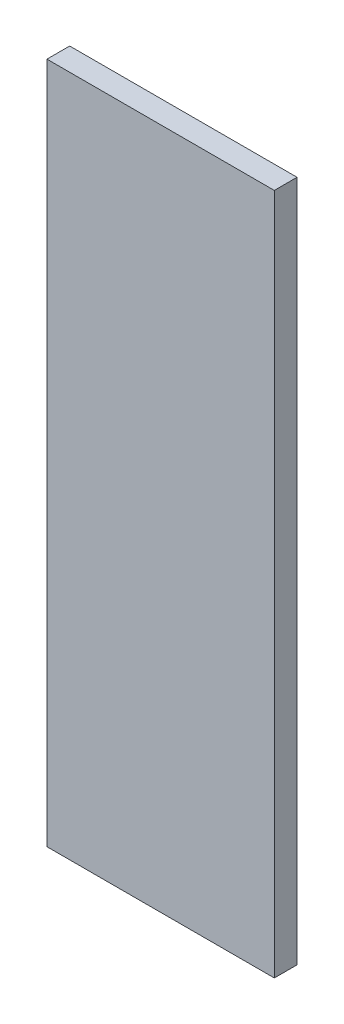
SolidWorks part; units mm, degrees
ref_plane "Front Plane" through (0, 0, 0) normal (0, 0, 1) x (1, 0, 0)
ref_plane "Top Plane" through (0, 0, 0) normal (0, 1, 0) x (1, 0, 0)
ref_plane "Right Plane" through (0, 0, 0) normal (1, 0, 0) x (0, 0, -1)
sketch "Sketch1" plane through (0, 0, 0) normal (0, 0, 1) x (1, 0, 0)
  line L1 (50, -150) -> (-50, -150)
  line L2 (50, -150) -> (50, 150)
  line L3 (50, 150) -> (-50, 150)
  line L4 (-50, -150) -> (-50, 150)
  line L5 (50, -150) -> (-50, 150) construction
  line L6 (50, 150) -> (-50, -150) construction
  point P0 (0, 0)
  dimension "D1" = 100
  dimension "D2" = 300
extrude "Boss-Extrude1" add sketch "Sketch1" along normal blind 10
sketch "Sketch2" plane through (0, 0, 10) normal (0, 0, 1) x (1, 0, 0)
  line L0 (-50, 150) -> (-50, -150) construction
  line L1 (50, 150) -> (-50, 150) construction
  line L2 (-50, -150) -> (50, -150) construction
  line L4 (0, -5.5) -> (0, 5.5) construction
  circle A0 centre (-45, 122) radius 1.5
  circle A1 centre (-45, 77) radius 1.5
  circle A2 centre (45, 122) radius 1.5
  circle A3 centre (45, 77) radius 1.5
  circle A4 centre (-45, 24) radius 1.5
  circle A5 centre (-45, -21) radius 1.5
  circle A6 centre (45, 24) radius 1.5
  circle A7 centre (45, -21) radius 1.5
  circle A8 centre (-45, -74) radius 1.5
  circle A9 centre (-45, -119) radius 1.5
  circle A10 centre (45, -74) radius 1.5
  circle A11 centre (45, -119) radius 1.5
  circle A13 centre (16.5, -147) radius 1.5
  circle A14 centre (-16.5, -147) radius 1.5
  circle A15 centre (-16.5, -49) radius 1.5
  circle A16 centre (16.5, -49) radius 1.5
  circle A17 centre (-16.5, 49) radius 1.5
  circle A18 centre (16.5, 49) radius 1.5
  circle A19 centre (-16.5, 147) radius 1.5
  circle A20 centre (16.5, 147) radius 1.5
  dimension "D1" = 3
  dimension "D3" = 28
  dimension "D4" = 3
  dimension "D6" = 5
  dimension "D10" = 3
  dimension "D11" = 33
  dimension "D13" = 3
  dimension "D2" = 5
  dimension "D5" = 45
  dimension "D9" = 31
  dimension "D7" = 2
  dimension "D8" = 3
  dimension "D12" = 4
